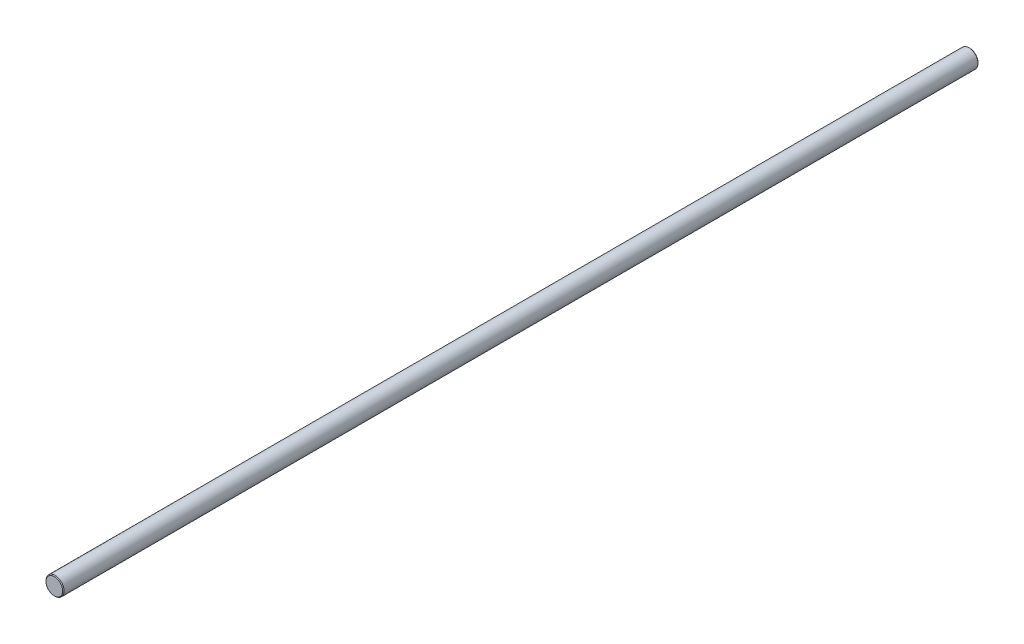
SolidWorks part; units mm, degrees
material "AISI 304"
ref_plane "Спереди" through (0, 0, 0) normal (0, 0, 1) x (1, 0, 0)
ref_plane "Сверху" through (0, 0, 0) normal (0, 1, 0) x (1, 0, 0)
ref_plane "Справа" through (0, 0, 0) normal (1, 0, 0) x (0, 0, -1)
ref_axis "ОсьX" through (-88.99, 0, 0) along (1, 0, 0)
ref_axis "ОсьZ" through (0, 55, 0) along (0, -1, 0)
ref_axis "ОсьY" through (0, 0, -88.99) along (0, 0, 1)
sketch "Эскиз1" plane through (0, 0, 0) normal (0, 0, 1) x (1, 0, 0)
  circle A0 centre (0, 0) radius 12.5
  dimension "D1" = 25
extrude "Бобышка-Вытянуть1" add sketch "Эскиз1" along normal mid plane 1264
chamfer "Фаска1" distance 1 angle 45 2 edges at (12.5, 0, -632) (12.5, 0, 632)
